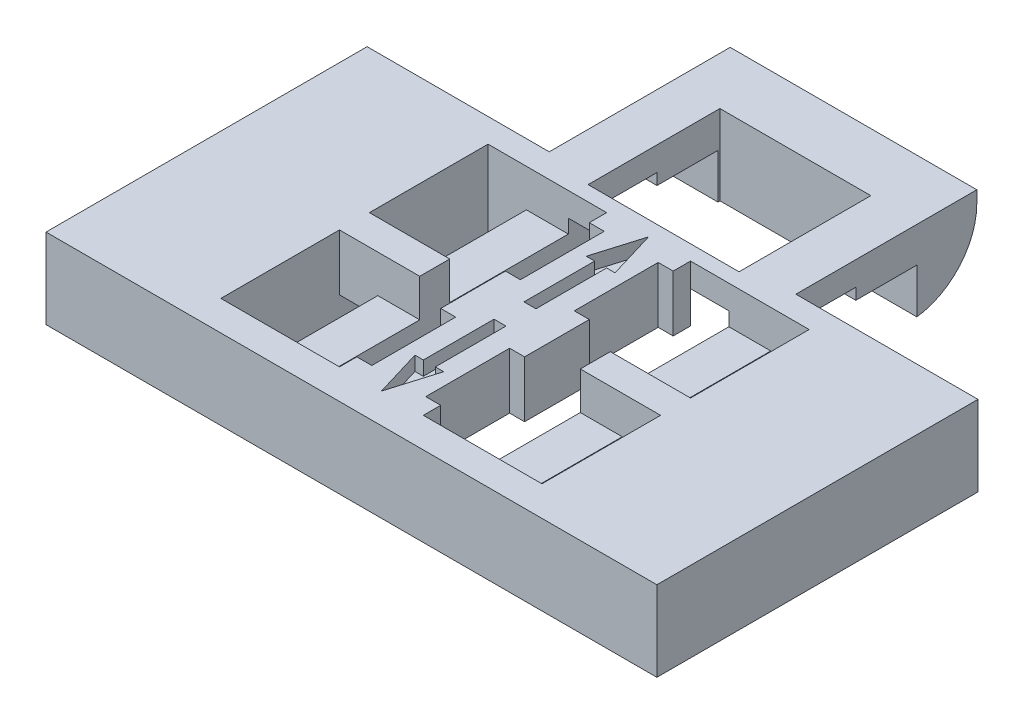
SolidWorks part; units mm, degrees
note: The reader was unsure of these and kept them because the rebuilt part matched: shared geometry of "Sketch1<3>", "Sketch8<3>", "Sketch8<4>".
ref_plane "Front Plane" through (0, 0, 0) normal (0, 0, 1) x (1, 0, 0)
ref_plane "Top Plane" through (0, 0, 0) normal (0, 1, 0) x (1, 0, 0)
ref_plane "Right Plane" through (0, 0, 0) normal (1, 0, 0) x (0, 0, -1)
sketch "Sketch1" plane through (0, 0, 0) normal (0, 1, 0) x (1, 0, 0)
  line L0 (-25.625, 13.5875) -> (-25.625, 16.7625)
  line L1 (32.375, 42.1625) -> (-32.375, 42.1625)
  line L2 (32.375, 42.1625) -> (32.375, -42.1625)
  line L3 (32.375, -42.1625) -> (-32.375, -42.1625)
  line L4 (-32.375, 42.1625) -> (-32.375, -42.1625)
  line L5 (32.375, 42.1625) -> (-32.375, -42.1625) construction
  line L6 (32.375, -42.1625) -> (-32.375, 42.1625) construction
  line L13 (-32.375, 13.5875) -> (-25.625, 13.5875)
  line L14 (-32.375, 13.5875) -> (-32.375, 6.8375)
  line L15 (-32.375, 6.8375) -> (-25.625, 6.8375)
  line L16 (-25.625, 13.5875) -> (-25.625, 6.8375)
  line L17 (-32.375, 13.5875) -> (-25.625, 6.8375) construction
  line L18 (-32.375, 6.8375) -> (-25.625, 13.5875) construction
  line L19 (25.625, 6.8375) -> (32.375, 6.8375)
  line L20 (25.625, 6.8375) -> (25.625, 13.5875)
  line L21 (25.625, 13.5875) -> (32.375, 13.5875)
  line L22 (32.375, 6.8375) -> (32.375, 13.5875)
  line L23 (25.625, 6.8375) -> (32.375, 13.5875) construction
  line L24 (25.625, 13.5875) -> (32.375, 6.8375) construction
  line L25 (25.625, -35.4125) -> (32.375, -35.4125)
  line L26 (25.625, -35.4125) -> (25.625, -42.1625)
  line L27 (25.625, -42.1625) -> (32.375, -42.1625)
  line L28 (32.375, -35.4125) -> (32.375, -42.1625)
  line L29 (25.625, -35.4125) -> (32.375, -42.1625) construction
  line L30 (25.625, -42.1625) -> (32.375, -35.4125) construction
  line L31 (-25.625, -35.4125) -> (-32.375, -35.4125)
  line L32 (-25.625, -35.4125) -> (-25.625, -42.1625)
  line L33 (-25.625, -42.1625) -> (-32.375, -42.1625)
  line L34 (-32.375, -35.4125) -> (-32.375, -42.1625)
  line L35 (-25.625, -35.4125) -> (-32.375, -42.1625) construction
  line L36 (-25.625, -42.1625) -> (-32.375, -35.4125) construction
  line L47 (-32.375, -42.1625) -> (32.375, -42.1625)
  line L56 (-25.625, 16.7625) -> (-32.375, 16.7625)
  line L58 (25.625, 13.5875) -> (25.625, 16.7625)
  line L59 (25.625, 16.7625) -> (32.375, 16.7625)
  circle A0 centre (-29, 10.2125) radius 1.35
  circle A1 centre (29, 10.2125) radius 1.35
  circle A2 centre (-29, -38.7875) radius 1.35
  circle A3 centre (29, -38.7875) radius 1.35
  point P0 (0, 0)
  point P27 (0, 0)
  dimension "D1" = 2.7
  dimension "D2" = 58
  dimension "D3" = 49
  dimension "D4" = 25.4
  dimension "D5" = 6.75
  dimension "D6" = 3.175
extrude "Boss-Extrude1" add sketch "Sketch1" along normal blind 25.4
sketch "Sketch3" plane through (32.375, 0, 0) normal (1, 0, 0) x (0, 0, -1)
  line L0 (42.1625, 18.034) -> (23.1125, 18.669)
  line L1 (42.1625, 25.4) -> (42.1625, 0) construction
  line L2 (23.1125, 18.669) -> (23.1125, 12.7)
  line L3 (23.1125, 12.7) -> (42.1625, 12.7)
  line L4 (42.1625, 12.7) -> (42.1625, 18.034)
  line L5 (42.1625, 0) -> (-42.1625, 0) construction
  dimension "D1" = 5.969
  dimension "D2" = 5.334
  dimension "D3" = 19.05
  dimension "D4" = 12.7
extrude "Cut-Extrude1" cut sketch "Sketch3" against normal through all
sketch "Sketch5" plane through (32.375, 0, 0) normal (1, 0, 0) x (0, 0, -1)
  line L0 (16.7625, 25.4) -> (16.7625, 4.7625)
  line L1 (42.1625, 25.4) -> (-42.1625, 25.4) construction
  line L2 (16.7625, 4.7625) -> (-42.1625, 4.7625)
  line L3 (-42.1625, 4.7625) -> (-42.1625, 25.4)
  line L4 (-42.1625, 25.4) -> (16.7625, 25.4)
  line L6 (42.1625, 0) -> (-42.1625, 0) construction
  dimension "D2" = 4.7625
extrude "Cut-Extrude3" cut sketch "Sketch5" against normal through all
extrude "Boss-Extrude2" add sketch "Sketch1<3>" along normal blind 6.35 from surface at 4.7625 contours L25 L26 L3 L2 A3 | L32 L31 L4 L3 A2 | L16 L13 L4 L15 A0 | L21 L20 L19 L2 A1 | L0 L56 L4 L13 | L59 L58 L21 L2 starting at face at (-29, 4.7625, 37.4375)
sketch "Sketch1<3>" plane through (0, 0, 0) normal (0, 1, 0) x (1, 0, 0) same geometry as "Sketch1"
sketch "Sketch7" plane through (0, 12.7, 0) normal (0, 1, 0) x (1, 0, 0)
  line L1 (-13.325, -29.4625) -> (13.325, -29.4625)
  line L2 (-13.325, -29.4625) -> (-13.325, 29.4625)
  line L3 (-13.325, 29.4625) -> (13.325, 29.4625)
  line L4 (13.325, -29.4625) -> (13.325, 29.4625)
  line L7 (32.375, -35.4125) -> (32.375, 6.8375) construction
  line L8 (32.375, 42.1625) -> (-32.375, 42.1625) construction
  point P4 (-13.325, 0)
  point P8 (0, -29.4625)
  dimension "D1" = 19.05
  dimension "D2" = 12.7
extrude "Cut-Extrude6" cut sketch "Sketch7" against normal through all both and the other way through all
sketch "Sketch8" plane through (0, 0, 0) normal (0, -1, 0) x (1, 0, 0)
  line L0 (25.625, 42.1625) -> (32.375, 42.1625) construction
  line L1 (-32.375, 42.1625) -> (32.375, 42.1625)
  line L2 (-32.375, 42.1625) -> (-32.375, 76.1985)
  line L3 (-32.375, 76.1985) -> (32.375, 76.1985)
  line L4 (32.375, 42.1625) -> (32.375, 76.1985)
  line L5 (-4.445, 50.989) -> (4.445, 50.989) construction
  line L6 (-17.018, 44.7025) -> (-4.445, 44.7025)
  line L7 (-17.018, 44.7025) -> (-17.018, 57.2755)
  line L8 (-17.018, 57.2755) -> (-4.445, 57.2755)
  line L9 (-4.445, 44.7025) -> (-4.445, 57.2755)
  line L10 (4.445, 44.7025) -> (17.018, 44.7025)
  line L11 (4.445, 44.7025) -> (4.445, 57.2755)
  line L12 (4.445, 57.2755) -> (17.018, 57.2755)
  line L13 (17.018, 44.7025) -> (17.018, 57.2755)
  line L14 (-20.828, 42.1625) -> (-20.828, 76.1985)
  line L15 (-8.509, 44.7025) -> (-12.954, 44.7025)
  line L16 (-8.509, 44.7025) -> (-8.509, 57.2755)
  line L17 (-8.509, 57.2755) -> (-12.954, 57.2755)
  line L18 (-12.954, 44.7025) -> (-12.954, 57.2755)
  line L19 (8.509, 44.7025) -> (12.954, 44.7025)
  line L20 (8.509, 44.7025) -> (8.509, 57.2755)
  line L21 (8.509, 57.2755) -> (12.954, 57.2755)
  line L22 (12.954, 44.7025) -> (12.954, 57.2755)
  line L23 (-4.445, 60.4505) -> (-17.018, 60.4505)
  line L24 (-4.445, 60.4505) -> (-4.445, 73.0235)
  line L25 (-4.445, 73.0235) -> (-17.018, 73.0235)
  line L26 (-17.018, 60.4505) -> (-17.018, 73.0235)
  line L27 (4.445, 60.4505) -> (17.018, 60.4505)
  line L28 (4.445, 60.4505) -> (4.445, 73.0235)
  line L29 (4.445, 73.0235) -> (17.018, 73.0235)
  line L30 (17.018, 60.4505) -> (17.018, 73.0235)
  line L31 (-8.509, 60.4505) -> (-12.954, 60.4505)
  line L32 (-8.509, 60.4505) -> (-8.509, 73.0235)
  line L33 (-8.509, 73.0235) -> (-12.954, 73.0235)
  line L34 (-12.954, 60.4505) -> (-12.954, 73.0235)
  line L39 (8.509, 60.4505) -> (12.954, 60.4505)
  line L40 (8.509, 60.4505) -> (8.509, 73.0235)
  line L41 (8.509, 73.0235) -> (12.954, 73.0235)
  line L42 (12.954, 60.4505) -> (12.954, 73.0235)
  line L43 (20.828, 42.1625) -> (20.828, 76.1985)
  line L44 (-4.445, 60.4505) -> (-4.445, 57.2755)
  line L45 (-8.509, 60.4505) -> (-8.509, 57.2755)
  line L46 (8.509, 57.2755) -> (8.509, 60.4505)
  line L47 (4.445, 57.2755) -> (4.445, 60.4505)
  line L48 (-3.6512, 68.642) -> (-3.6512, 64.832) construction
  line L49 (-4.445, 62.292) -> (-2.8575, 62.292)
  line L50 (-4.445, 62.292) -> (-4.445, 64.832)
  line L51 (-4.445, 64.832) -> (-2.8575, 64.832)
  line L52 (-2.8575, 62.292) -> (-2.8575, 64.832)
  line L53 (-4.445, 71.182) -> (-2.8575, 71.182)
  line L54 (-4.445, 71.182) -> (-4.445, 68.642)
  line L55 (-4.445, 68.642) -> (-2.8575, 68.642)
  line L56 (-2.8575, 71.182) -> (-2.8575, 68.642)
  line L65 (-4.445, 55.434) -> (-2.8575, 55.434)
  line L66 (-4.445, 55.434) -> (-4.445, 52.894)
  line L67 (-4.445, 52.894) -> (-2.8575, 52.894)
  line L68 (-2.8575, 55.434) -> (-2.8575, 52.894)
  line L69 (-4.445, 46.544) -> (-2.8575, 46.544)
  line L70 (-4.445, 46.544) -> (-4.445, 49.084)
  line L71 (-4.445, 49.084) -> (-2.8575, 49.084)
  line L72 (-2.8575, 46.544) -> (-2.8575, 49.084)
  line L81 (-3.6512, 52.894) -> (-3.6512, 49.084) construction
  line L82 (-4.445, 66.737) -> (4.445, 66.737) construction
  line L83 (0, 76.1985) -> (0, 42.1625) construction
  line L84 (4.445, 68.642) -> (2.8575, 68.642)
  line L85 (2.8575, 71.182) -> (2.8575, 68.642)
  line L86 (4.445, 71.182) -> (2.8575, 71.182)
  line L87 (4.445, 71.182) -> (4.445, 68.642)
  line L88 (4.445, 64.832) -> (2.8575, 64.832)
  line L89 (2.8575, 62.292) -> (2.8575, 64.832)
  line L90 (4.445, 62.292) -> (2.8575, 62.292)
  line L91 (4.445, 62.292) -> (4.445, 64.832)
  line L92 (4.445, 52.894) -> (2.8575, 52.894)
  line L93 (2.8575, 55.434) -> (2.8575, 52.894)
  line L94 (4.445, 55.434) -> (2.8575, 55.434)
  line L95 (4.445, 55.434) -> (4.445, 52.894)
  line L96 (4.445, 49.084) -> (2.8575, 49.084)
  line L97 (2.8575, 46.544) -> (2.8575, 49.084)
  line L98 (4.445, 46.544) -> (2.8575, 46.544)
  line L99 (4.445, 46.544) -> (4.445, 49.084)
  line L100 (2.8575, 49.084) -> (2.8575, 52.894)
  line L101 (2.8575, 64.832) -> (2.8575, 68.642)
  line L102 (-2.8575, 64.832) -> (-2.8575, 68.642)
  line L103 (-2.8575, 49.084) -> (-2.8575, 52.894)
  line L104 (4.445, 44.7025) -> (-4.445, 44.7025)
  line L105 (4.445, 73.0235) -> (-4.445, 73.0235)
  point P17 (0, 50.989)
  point P18 (0, 76.1985)
  point P26 (-10.7315, 57.2755)
  point P27 (-10.7315, 57.2755)
  point P28 (10.7315, 57.2755)
  point P33 (10.7315, 57.2755)
  point P64 (-3.6512, 50.989)
  point P67 (-3.6512, 66.737)
  dimension "D1" = 2.54
  dimension "D2" = 12.573
  dimension "D3" = 8.89
  dimension "D4" = 4.445
  dimension "D5" = 3.175
  dimension "D6" = 3.175
  dimension "D7" = 3.81
  dimension "D8" = 3.81
  dimension "D9" = 2.54
  dimension "D10" = 1.5875
  dimension "D11" = 3.81
extrude "Boss-Extrude3" add sketch "Sketch8" against normal blind 8.5
extrude "Cut-Extrude7" cut sketch "Sketch8<3>" along normal blind 4 from surface at -8.5 contours L18 L6 L16 L8 | L10 L22 L12 L20 | L34 L23 L32 L25 | L27 L42 L29 L40 starting at face at (4.5932, 8.5, 58.863)
sketch "Sketch8<3>" plane through (0, 0, 0) normal (0, -1, 0) x (1, 0, 0) same geometry as "Sketch8"
extrude "Cut-Extrude8" cut sketch "Sketch8<4>" against normal blind 2.54 contours L10 L22 L12 L20 | L18 L6 L16 L8 | L27 L42 L29 L40 | L34 L23 L32 L25 | L28 L105 L24 L53 L56 L102 L52 L49 L44 L9 L65 L68 L103 L72 L69 L104 L11 L98 L97 L100 L93 L94 L47 L90 L89 L101 L85 L86
sketch "Sketch8<4>" plane through (0, 0, 0) normal (0, -1, 0) x (1, 0, 0) same geometry as "Sketch8"
sketch "Sketch9" plane through (0, 0, 0) normal (0, -1, 0) x (1, 0, 0)
  line L1 (-13.325, -42.1625) -> (13.325, -42.1625)
  line L2 (-13.325, -42.1625) -> (-13.325, 44.7025)
  line L3 (-13.325, 44.7025) -> (13.325, 44.7025)
  line L4 (13.325, -42.1625) -> (13.325, 44.7025)
  line L8 (-13.325, -29.4625) -> (-13.325, 29.4625) construction
  line L9 (13.325, 29.4625) -> (13.325, -29.4625) construction
  line L11 (-12.954, 44.7025) -> (-8.509, 44.7025) construction
  line L12 (32.375, -42.1625) -> (-32.375, -42.1625) construction
  line L18 (-17.018, 60.4505) -> (-8.509, 60.4505)
  line L19 (-17.018, 60.4505) -> (-17.018, 57.2755)
  line L20 (-17.018, 57.2755) -> (-8.509, 57.2755)
  line L21 (-8.509, 60.4505) -> (-8.509, 57.2755)
  line L22 (8.509, 60.4505) -> (17.018, 60.4505)
  line L23 (8.509, 60.4505) -> (8.509, 57.2755)
  line L24 (8.509, 57.2755) -> (17.018, 57.2755)
  line L25 (17.018, 60.4505) -> (17.018, 57.2755)
  point P4 (-6.35, 57.4025)
  point P21 (6.35, 57.4025)
  point P22 (6.35, 60.5775)
extrude "Cut-Extrude9" cut sketch "Sketch9" against normal up to surface (2.54 mm away) up to face at (-10.7315, 2.54, 50.989)
sketch "Sketch10" plane through (0, 8.5, 0) normal (0, 1, 0) x (1, 0, 0)
  line L0 (4.445, -55.434) -> (4.445, -62.292) construction
  line L2 (-4.445, -55.434) -> (-4.445, -62.292) construction
  line L7 (-0.635, -57.2755) -> (0.635, -57.2755)
  line L8 (0.635, -57.2755) -> (0.635, -49.7825)
  line L9 (0.635, -49.7825) -> (1.524, -49.7825)
  line L10 (1.524, -49.7825) -> (0, -44.7025)
  line L11 (0, -44.7025) -> (-1.524, -49.7825)
  line L12 (-1.524, -49.7825) -> (-0.635, -49.7825)
  line L13 (-0.635, -49.7825) -> (-0.635, -57.2755)
  line L14 (-4.445, -57.2755) -> (-4.445, -60.4505) construction
  line L15 (-4.445, -58.863) -> (4.445, -58.863) construction
  line L16 (4.445, -57.2755) -> (4.445, -60.4505) construction
  line L17 (-0.635, -67.9435) -> (-0.635, -60.4505)
  line L18 (-1.524, -67.9435) -> (-0.635, -67.9435)
  line L19 (0, -73.0235) -> (-1.524, -67.9435)
  line L20 (1.524, -67.9435) -> (0, -73.0235)
  line L21 (0.635, -67.9435) -> (1.524, -67.9435)
  line L22 (0.635, -60.4505) -> (0.635, -67.9435)
  line L23 (-0.635, -60.4505) -> (0.635, -60.4505)
  point P2 (3.175, -60.7037)
  point P10 (0, 0)
  point P13 (-1.3225, -57.4025)
  point P14 (0, 0)
  point P15 (0, -57.2755)
  point P24 (0, 0)
  point P25 (0, -58.863)
  point P26 (0, 0)
  point P27 (-3.175, -57.4025)
  point P31 (0, 0)
  dimension "D1" = 1.27
  dimension "D2" = 0.889
  dimension "D3" = 5.08
extrude "Cut-Extrude10" cut sketch "Sketch10" against normal blind 1.5
ref_plane "Plane1" through (0, 4.7625, 0) normal (0, 1, 0) x (1, 0, 0)
sketch "Sketch11" plane through (0, 0, 0) normal (0, -1, 0) x (1, 0, 0)
  line L5 (-32.375, 42.1625) -> (32.375, 42.1625)
  line L6 (-32.375, 42.1625) -> (-32.375, -42.1625)
  line L7 (-32.375, -42.1625) -> (32.375, -42.1625)
  line L8 (32.375, 42.1625) -> (32.375, -42.1625)
extrude "Cut-Extrude11" cut sketch "Sketch11" against normal through all
sketch "Sketch14" plane through (32.375, 0, 0) normal (1, 0, 0) x (0, 0, -1)
  line L0 (-42.1625, 8.5) -> (-22.9855, 8.5)
  line L2 (-29.3355, 0) -> (-29.3355, 4.7625)
  line L3 (-29.3355, 4.7625) -> (-42.1625, 4.7625)
  line L5 (-42.1625, 4.7625) -> (-42.1625, 8.5)
  line L6 (-22.9855, 8.5) -> (-22.9855, 7.23)
  line L7 (55, 4.7625) -> (-55, 4.7625) construction
  line L8 (-29.4625, 0) -> (-29.4625, 12.7) construction
  line L9 (-42.1625, 0) -> (42.1625, 0) construction
  line L11 (-42.1625, 4.7625) -> (-35.8125, 4.7625)
  line L12 (-42.1625, 4.7625) -> (-42.1625, 5.96)
  line L13 (-42.1625, 5.96) -> (-35.8125, 5.96)
  line L14 (-35.8125, 4.7625) -> (-35.8125, 5.96)
  arc A2 (-22.9855, 7.23) -> (-29.3355, 0) centre (-30.2765, 7.23) cw
  point P7 (0, 0)
  point P11 (-42.1625, 8.5)
  point P13 (0, 0)
  dimension "D1" = 0.254
  dimension "D2" = 6.35
  dimension "D3" = 1.27
  dimension "D4" = 6.35
  dimension "D5" = 2.54
extrude "Boss-Extrude4" add sketch "Sketch14" against normal up to surface (64.75 mm away) contours L3 L8 L0 L5 L13 L14 | L8 L3 L2 A2 L6 L0 up to face at (-32.375, 4.25, 59.1805)
sketch "Sketch15" plane through (0, 8.5, 0) normal (0, 1, 0) x (1, 0, 0)
  line L0 (-32.375, -22.9855) -> (32.375, -22.9855) construction
  line L1 (-32.375, -42.1625) -> (-13.071, -42.1625)
  line L2 (-32.375, -42.1625) -> (-32.375, -22.9855)
  line L3 (-32.375, -22.9855) -> (-13.071, -22.9855)
  line L4 (-13.071, -42.1625) -> (-13.071, -22.9855)
  line L5 (-13.325, -29.4625) -> (-13.325, 29.4625) construction
  line L6 (32.375, -42.1625) -> (13.071, -42.1625)
  line L7 (32.375, -42.1625) -> (32.375, -22.9855)
  line L8 (32.375, -22.9855) -> (13.071, -22.9855)
  line L9 (13.071, -42.1625) -> (13.071, -22.9855)
  line L10 (13.325, -29.4625) -> (13.325, 29.4625) construction
  line L12 (-8, -29.145) -> (8, -29.145)
  line L13 (-8, -29.145) -> (-8, -43.115)
  line L14 (-8, -43.115) -> (8, -43.115)
  line L15 (8, -29.145) -> (8, -43.115)
  line L26 (-13.071, -42.1625) -> (-13.071, -44.7025) construction
  line L27 (-17.018, -44.7025) -> (-4.445, -44.7025) construction
  line L28 (-32.375, -22.9855) -> (-32.375, -76.1985) construction
  line L29 (32.375, -22.9855) -> (32.375, -76.1985) construction
  line L30 (-17.018, -44.7025) -> (-4.445, -44.7025) construction
  line L31 (32.375, -42.1625) -> (13.325, -42.1625) construction
  point P20 (0, 0)
  point P23 (0, -29.145)
  point P24 (0, -22.9855)
  point P25 (0, 0)
  point P26 (-32.375, -43.4208)
  point P27 (0, 0)
  point P29 (32.375, -40.4242)
  point P35 (0, 0)
  point P39 (0, 0)
  point P40 (0, 0)
  dimension "D1" = 0.254
  dimension "D2" = 0.254
  dimension "D3" = 16
  dimension "D4" = 13.97
  dimension "D5" = 1.5875
extrude "Cut-Extrude12" cut sketch "Sketch15" against normal through all contours L1 L4 L3 L2 | L15 L12 L13 L14 | L9 L6 L7 L8
sketch "Sketch17" plane through (0, 0, 0) normal (0, -1, 0) x (1, 0, 0)
  line L0 (8.509, 44.7025) -> (8.509, 42.1625)
  line L1 (13.325, 42.1625) -> (8, 42.1625) construction
  line L2 (8.509, 42.1625) -> (-8.509, 42.1625)
  line L3 (-8, 42.1625) -> (-13.325, 42.1625) construction
  line L4 (-8.509, 42.1625) -> (-8.509, 44.7025)
  line L5 (-8.509, 44.7025) -> (8.509, 44.7025)
extrude "Cut-Extrude13" cut sketch "Sketch17" against normal up to surface (5.96 mm away) up to face at (10.5355, 5.96, 38.9875)
